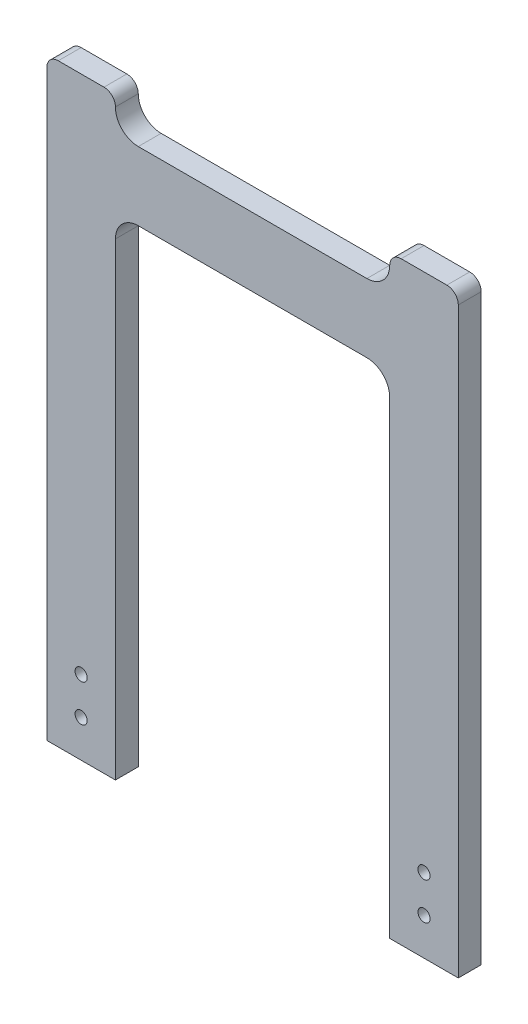
SolidWorks part; units mm, degrees
ref_plane "Front Plane" through (0, 0, 0) normal (0, 0, 1) x (1, 0, 0)
ref_plane "Top Plane" through (0, 0, 0) normal (0, 1, 0) x (1, 0, 0)
ref_plane "Right Plane" through (0, 0, 0) normal (1, 0, 0) x (0, 0, -1)
sketch "Sketch1" plane through (0, 0, 0) normal (0, 0, 1) x (1, 0, 0)
  line L0 (-114.3, -31.75) -> (-76.2, -31.75)
  line L1 (-76.2, -31.75) -> (-76.2, 241.3)
  line L2 (-76.2, 241.3) -> (76.2, 241.3)
  line L3 (76.2, 241.3) -> (76.2, -31.75)
  line L4 (76.2, -31.75) -> (114.3, -31.75)
  line L5 (114.3, -31.75) -> (114.3, 298.45)
  line L6 (114.3, 298.45) -> (76.2, 298.45)
  line L7 (76.2, 298.45) -> (76.2, 279.4)
  line L8 (76.2, 279.4) -> (-76.2, 279.4)
  line L9 (-76.2, 279.4) -> (-76.2, 298.45)
  line L10 (-76.2, 298.45) -> (-114.3, 298.45)
  line L11 (-114.3, 298.45) -> (-114.3, -31.75)
  line L12 (0, 241.3) -> (0, 0) construction
  dimension "D2" = 31.75
  dimension "D1" = 330.2
  dimension "D3" = 228.6
  dimension "D4" = 19.05
  dimension "D5" = 38.1
  dimension "D7" = 38.1
extrude "Boss-Extrude1" add sketch "Sketch1" along normal blind 12.7
hole_wizard "1/4 Clearance Hole1" positions "Sketch2" profile "Sketch3" hole size "1/4" standard "ANSI Inch"
sketch "Sketch2" plane through (0, 0, 12.7) normal (0, 0, 1) x (1, 0, 0)
  line L0 (0, 0) -> (0, 50000) construction
  line L1 (-114.3, -31.75) -> (-76.2, -31.75) construction
  point P0 (-95.25, -11.1125)
  point P2 (-95.25, 9.525)
  point P4 (95.25, -11.1125)
  point P6 (95.25, 9.525)
  point P26 (-95.25, -31.75)
  dimension "D1" = 20.6375
  dimension "D2" = 20.6375
sketch "Sketch3" plane through (-95.25, -11.1125, 12.7) normal (1, 0, 0) x (0, -1, 0)
  line L0 (0, 0) -> (0, 221.9938)
  line L1 (0, 221.9938) -> (3.3782, 219.964)
  line L2 (3.3782, 219.964) -> (3.3782, 0)
  line L5 (3.3782, 0) -> (0, 0)
  line L10 (0, 221.9938) -> (-3.3782, 219.964) construction
  line L11 (0, -6.35) -> (0, 107.95) construction
  dimension "Hole Dia." = 6.7564
  dimension "Hole Depth" = 219.964
  dimension "Drill Angle" = 118
fillet "Fillet1" radius 12.7 4 edges at (76.2, 241.3, 6.35) (76.2, 279.4, 6.35) (-76.2, 241.3, 6.35) (-76.2, 279.4, 6.35)
fillet "Fillet2" radius 6.35 4 edges at (114.3, 298.45, 6.35) (76.2, 298.45, 6.35) (-114.3, 298.45, 6.35) (-76.2, 298.45, 6.35)
